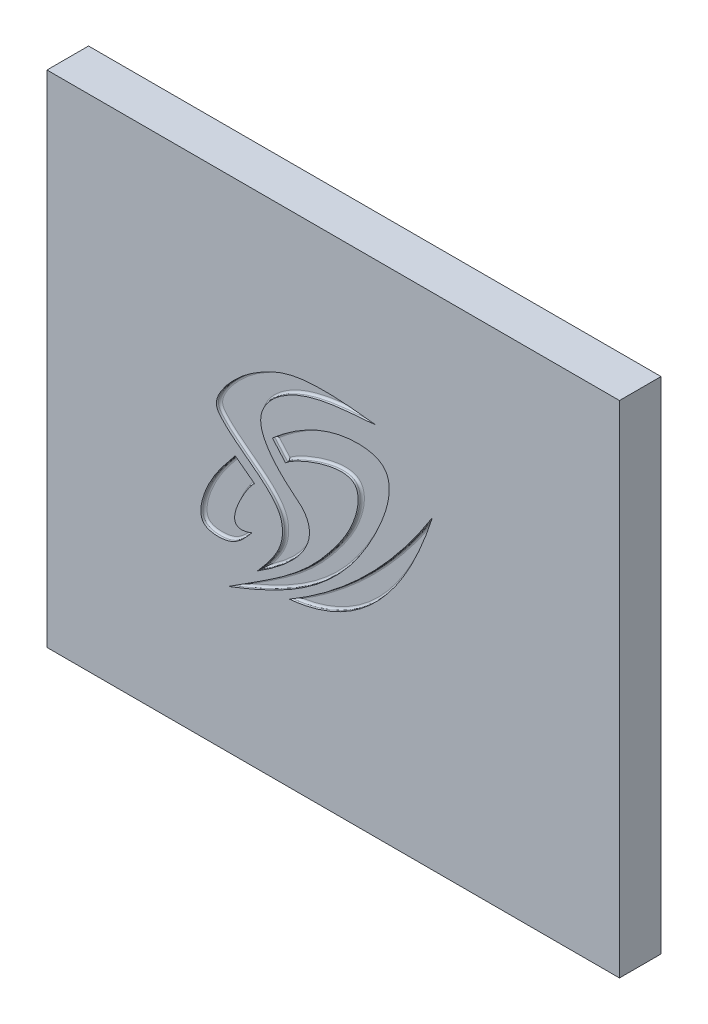
SolidWorks part; units mm, degrees
ref_plane "Front Plane" through (0, 0, 0) normal (0, 0, 1) x (1, 0, 0)
ref_plane "Top Plane" through (0, 0, 0) normal (0, 1, 0) x (1, 0, 0)
ref_plane "Right Plane" through (0, 0, 0) normal (1, 0, 0) x (0, 0, -1)
sketch "Sketch2" plane through (0, 0, 0) normal (0, 0, 1) x (1, 0, 0)
  line L1 (-37.0687, -32.8596) -> (100.7228, -32.8596)
  line L2 (-37.0687, -32.8596) -> (-37.0687, 87.5111)
  line L3 (-37.0687, 87.5111) -> (100.7228, 87.5111)
  line L4 (100.7228, -32.8596) -> (100.7228, 87.5111)
  point P0 (0, 0)
extrude "Boss-Extrude1" add sketch "Sketch2" along normal blind 10
sketch "Sketch1" plane through (0, 0, 0) normal (0, 0, 1) x (1, 0, 0)
  line L0 (20.3776, 34.2941) -> (17.1761, 37.9406)
  line L1 (8.2374, 29.7469) -> (12.9609, 26.1951)
  spline S0 degree 3 poles (41.9315, 53.1055) (25.4453, 55.1206) (19.2305, 53.3175) (8.3782, 46.575) (2.3295, 39.2351) (7.9343, 31.8488) (18.9044, 26.613) (19.9579, 17.528) (18.3926, 13.8395) (13.5627, 8.3952) knots 0 0 0 0 0.176334 0.210774 0.329554 0.388267 0.739198 0.804758 1 1 1 1
  spline S1 degree 3 poles (41.9315, 53.1055) (38.8693, 52.5589) (24.1172, 52.8957) (9.7234, 40.3381) (20.2317, 30.1811) (25.8652, 26.0103) (28.9523, 18.0568) (13.5627, 8.3952) knots 0 0 0 0 0.313518 0.565749 0.823695 0.86712 1 1 1 1
  spline S2 degree 2 poles (55.7004, 40.5848) (45.4362, 8.6475) (21.2829, 6.3889) knots 0 0 0 1 1 1
  spline S3 degree 2 poles (21.2829, 6.3889) (41.63, 18.2616) (55.7004, 40.5848) knots 0 0 0 1 1 1
  spline S4 degree 3 poles (17.1761, 37.9406) (20.6877, 40.9337) (29.5966, 47.6866) (48.7462, 47.0933) (37.4569, 15.3338) (20.5292, 7.0646) (6.6145, 1.7065) knots 0 0 0 0 0.203362 0.322878 0.508122 1 1 1 1
  spline S5 degree 3 poles (20.3776, 34.2941) (21.7988, 36.0449) (40.601, 44.3813) (37.1468, 29.6656) (25.9724, 13.4079) (18.7646, 9.5587) (6.6145, 1.7065) knots 0 0 0 0 0.260917 0.422294 0.496202 1 1 1 1
  spline S6 degree 3 poles (8.2374, 29.7469) (6.3869, 27.414) (0.9017, 21.5135) (-0.8448, 11.1693) (7.2343, 10.4593) (9.7885, 12.7224) (12.2593, 15.7043) knots 0 0 0 0 0.420232 0.607547 0.741967 1 1 1 1
  spline S7 degree 3 poles (12.9609, 26.1951) (12.4234, 26.9064) (2.7558, 11.9911) (12.2593, 15.7043) knots 0 0 0 0 1 1 1 1
extrude "Cut-Extrude3" cut sketch "Sketch1" against normal blind 1 from surface at 10 contours S3 S2 | S1 S0 | S7 L1 S6 | S5 S4 L0
fillet "Fillet1" radius 0.5 10 edges at (10.5854, 27.9813, 9) (18.7769, 36.1173, 9)
